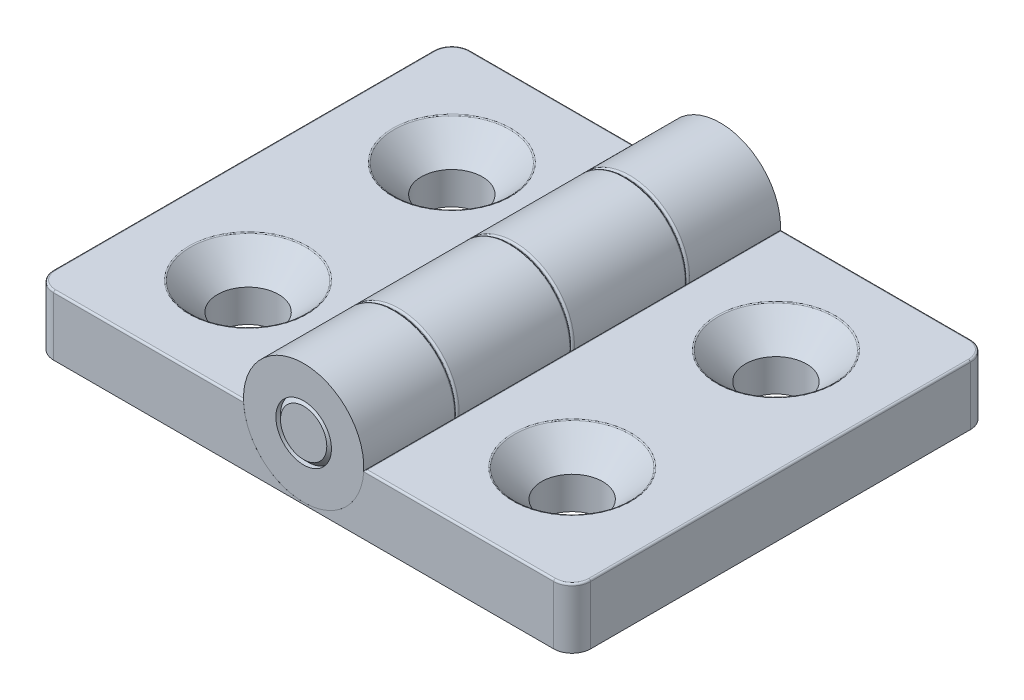
SolidWorks part; units mm, degrees
ref_plane "前视基准面" through (0, 0, 0) normal (0, 0, 1) x (1, 0, 0)
ref_plane "上视基准面" through (0, 0, 0) normal (0, 1, 0) x (1, 0, 0)
ref_plane "右视基准面" through (0, 0, 0) normal (1, 0, 0) x (0, 0, -1)
sketch "草图1" plane through (0, 0, 0) normal (0, 0, 1) x (1, 0, 0)
  circle A0 centre (0, 0) radius 6.5
  circle A1 centre (0, 0) radius 3
  dimension "D1" = 13
  dimension "D2" = 6
extrude "凸台-拉伸1" add sketch "草图1" along normal mid plane 45
sketch "草图2" plane through (0, 0, 0) normal (0, 0, 1) x (1, 0, 0)
  circle A0 centre (0, 0) radius 3
  dimension "D1" = 6
extrude "凸台-拉伸2" add sketch "草图2" along normal mid plane 45 separate body
chamfer "倒角1" distance 0.5 angle 45 1 edges at (3, 0, 22.5)
sketch "草图3" plane through (0, 0, 0) normal (0, 1, 0) x (1, 0, 0)
  line L0 (0, 0) -> (14.2235, 0) construction
  line L1 (7.1978, 12.5) -> (4.6777, 12.5)
  line L2 (7.1978, 12.5) -> (7.1978, 12.4)
  line L3 (7.1978, 12.4) -> (4.6777, 12.4)
  line L4 (4.6777, 12.5) -> (4.6777, 12.4)
  line L5 (6.5, 22.5) -> (-6.5, 22.5) construction
  line L6 (-6.5, -22.5) -> (6.5, -22.5) construction
  line L9 (7.1978, 0.05) -> (4.6777, 0.05)
  line L10 (7.1978, 0.05) -> (7.1978, -0.05)
  line L11 (7.1978, -0.05) -> (4.6777, -0.05)
  line L12 (4.6777, 0.05) -> (4.6777, -0.05)
  line L13 (7.1978, -12.4) -> (4.8947, -12.4)
  line L14 (7.1978, -12.4) -> (7.1978, -12.5)
  line L15 (7.1978, -12.5) -> (4.8947, -12.5)
  line L16 (4.8947, -12.4) -> (4.8947, -12.5)
  point P4 (7.1978, 0)
  dimension "D1" = 10
  dimension "D2" = 0.1
  dimension "D3" = 10
revolve "切除-旋转1" cut sketch "草图3" angle 360 about axis through (0, 0, 22.5) along (0, 0, -1)
fillet "圆角1" radius 0.2 6 edges at (6.5, 0, 12.5) (-6.5, 0, 12.4) (6.5, 0, 0.05) (-6.5, 0, -0.05) (6.5, 0, -12.4) (-6.5, 0, -12.5)
sketch "草图4" plane through (0, 0, 0) normal (0, 1, 0) x (1, 0, 0)
  line L0 (-6.5, -22.5) -> (6.5, -22.5) construction
  line L1 (-19.5, 22.5) -> (19.5, 22.5)
  line L2 (-19.5, 22.5) -> (-19.5, -22.5)
  line L3 (-19.5, -22.5) -> (19.5, -22.5)
  line L4 (19.5, 22.5) -> (19.5, -22.5)
  line L5 (6.5, 22.5) -> (-6.5, 22.5) construction
  point P4 (0, -22.5)
  dimension "D1" = 39
sketch "草图5" plane through (0, 0, -22.5) normal (0, 0, -1) x (-1, 0, 0)
  line L0 (6.4969, -0.2) -> (29, -0.2)
  line L3 (-29, -0.2) -> (-6.4969, -0.2)
  line L4 (-29, -0.2) -> (-29, -6.7)
  line L5 (-29, -6.7) -> (29, -6.7)
  line L6 (29, -0.2) -> (29, -6.7)
  circle A0 centre (0, 0) radius 6.5 construction
  arc A1 (-6.4969, -0.2) -> (6.4969, -0.2) centre (0, 0) ccw
  dimension "D2" = 0.2
  dimension "D4" = 29
  dimension "D1" = 6.5
  dimension "D3" = 58
extrude "凸台-拉伸6" add sketch "草图5" against normal up to surface (45 mm away) separate body up to face at (6.5, 0, 22.5)
hole_wizard "M6 平头机械螺钉的锥形沉头孔1" positions "草图7" profile "草图6" countersink size "M6" standard "Ansi Metric" end condition through all
sketch "草图7" plane through (0, -0.2, 0) normal (0, 1, 0) x (-1, 0, 0)
  line L0 (0, 0) -> (0, 18.3669) construction
  line L2 (0, 0) -> (27.3768, 0) construction
  point P1 (17.5, -11)
  point P3 (-17.5, -11)
  point P5 (17.5, 11)
  point P7 (-17.5, 11)
  dimension "D1" = 35
  dimension "D2" = 22
sketch "草图6" plane through (-17.5, -0.2, -11) normal (1, 0, 0) x (0, 0, 1)
  line L0 (0, 0) -> (0, 6.5)
  line L1 (0, 6.5) -> (3.3, 6.5)
  line L2 (3.3, 6.5) -> (3.3, 3)
  line L3 (3.3, 3) -> (6.3, 0)
  line L5 (6.3, 0) -> (0, 0)
  line L6 (-3.3, 3) -> (-6.3, 0) construction
  line L11 (0, -6.35) -> (0, 107.95) construction
  dimension "通孔孔直径" = 6.6
  dimension "通孔孔深度" = 6.5
  dimension "近端锥形沉头孔直径" = 12.6
  dimension "近端锥形沉头孔角度" = 90
fillet "圆角2" radius 0.2 12 edges at (17.7485, -0.2, -22.5) (29, -0.2, 0) (17.7485, -0.2, 22.5) (6.4969, -0.2, 0) (17.5, -0.2, 17.3) (17.5, -0.2, -4.7) (-17.7485, -0.2, -22.5) (-6.4969, -0.2, 0) (-17.7485, -0.2, 22.5) (-29, -0.2, 0) (-17.5, -0.2, 17.3) (-17.5, -0.2, -4.7)
fillet "圆角3" radius 2 8 edges at (-28.9414, -0.2586, -22.4414) (28.9414, -0.2586, -22.4414) (28.9414, -0.2586, 22.4414) (-28.9414, -0.2586, 22.4414) (-29, -3.55, 22.5) (29, -3.55, 22.5) (29, -3.55, -22.5) (-29, -3.55, -22.5)
chamfer "倒角2" distance 0.5 angle 45 1 edges at (3, 0, -22.5)
